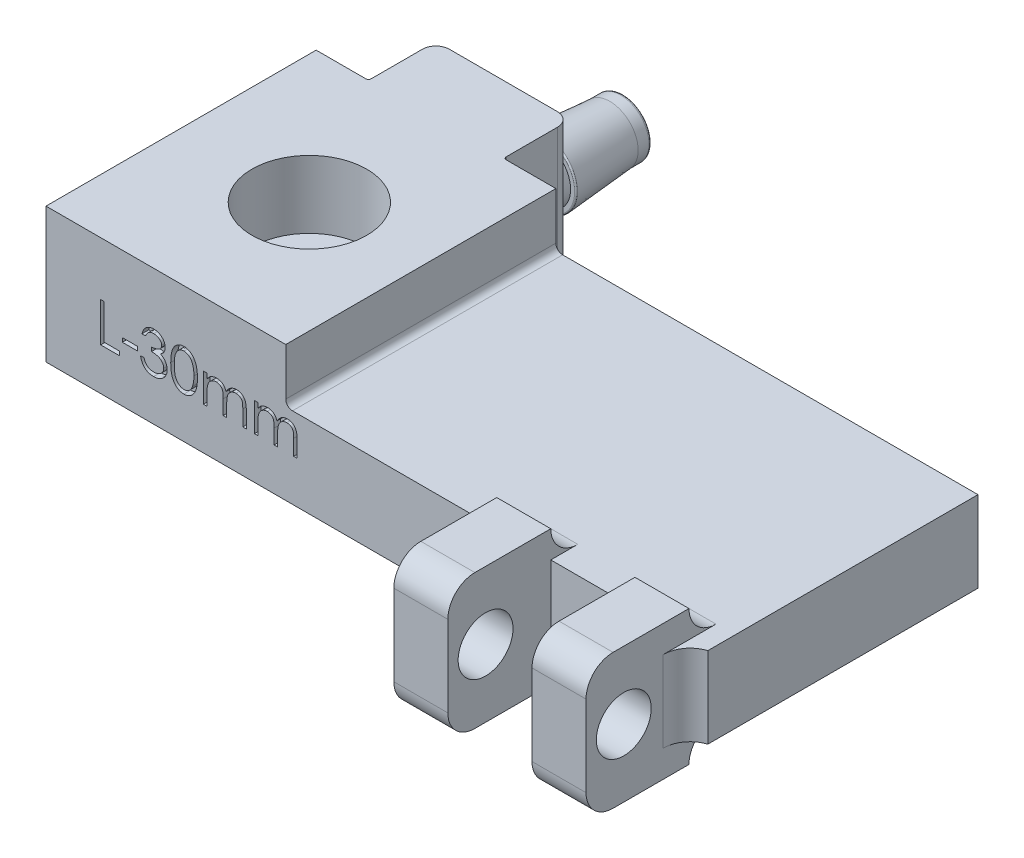
SolidWorks part; units mm, degrees
ref_plane "Front Plane" through (0, 0, 0) normal (0, 0, 1) x (1, 0, 0)
ref_plane "Top Plane" through (0, 0, 0) normal (0, 1, 0) x (1, 0, 0)
ref_plane "Right Plane" through (0, 0, 0) normal (1, 0, 0) x (0, 0, -1)
sketch "Sketch2" plane through (0, 0, 0) normal (0, 1, 0) x (1, 0, 0)
  line L1 (-14.4231, 13.5577) -> (34.5769, 13.5577)
  line L2 (-14.4231, 13.5577) -> (-14.4231, -6.4423)
  line L3 (-14.4231, -6.4423) -> (34.5769, -6.4423)
  line L4 (34.5769, 13.5577) -> (34.5769, -6.4423)
  dimension "D1" = 49
  dimension "D2" = 20
extrude "Boss-Extrude1" add sketch "Sketch2" along normal blind 10
sketch "Sketch3" plane through (0, 0, 0) normal (0, -1, 0) x (1, 0, 0)
  line L0 (34.5769, 6.4423) -> (34.5769, -13.5577) construction
  line L1 (27.5769, -5.0677) -> (-2.4231, -5.0677)
  line L2 (27.5769, -5.0677) -> (27.5769, -2.0477)
  line L3 (27.5769, -2.0477) -> (-2.4231, -2.0477)
  line L4 (-2.4231, -5.0677) -> (-2.4231, -2.0477)
  line L5 (-14.4231, -3.5577) -> (34.5769, -3.5577) construction
  line L6 (-14.4231, -13.5577) -> (-14.4231, 6.4423) construction
  dimension "D1" = 30
  dimension "D2" = 7
  dimension "D3" = 3.02
  dimension "D4" = 1.51
extrude "Cut-Extrude1" cut sketch "Sketch3" against normal blind 2
sketch "Sketch4" plane through (0, 0, 0) normal (0, -1, 0) x (1, 0, 0)
  line L0 (-2.4231, -2.0477) -> (-2.4231, -5.0677) construction
  line L1 (-2.4231, -6.5477) -> (-7.4231, -6.5477)
  line L2 (-2.4231, -6.5477) -> (-2.4231, -0.5477)
  line L3 (-2.4231, -0.5477) -> (-7.4231, -0.5477)
  line L4 (-7.4231, -6.5477) -> (-7.4231, -0.5477)
  line L6 (27.5769, -2.0477) -> (-2.4231, -2.0477) construction
  dimension "D1" = 6
  dimension "D2" = 5
  dimension "D3" = 1.5
extrude "Cut-Extrude2" cut sketch "Sketch4" against normal blind 5
sketch "Sketch5" plane through (0, 5, 0) normal (0, -1, 0) x (1, 0, 0)
  line L0 (-7.4231, -3.5477) -> (-2.4231, -3.5577) construction
  line L1 (-7.4231, -0.5477) -> (-7.4231, -6.5477) construction
  line L2 (-2.4231, -2.0477) -> (-2.4231, -5.0677) construction
  circle A0 centre (-4.9231, -3.5527) radius 4.25
  dimension "D1" = 8.5
extrude "Cut-Extrude3" cut sketch "Sketch5" against normal through all
sketch "Sketch6" plane through (0, 5, 0) normal (0, 1, 0) x (1, 0, 0)
  line L0 (-4.0731, 0.5477) -> (-2.4231, 0.5477)
  line L1 (-7.4231, 6.5477) -> (-5.7731, 6.5477)
  line L2 (-7.4231, 6.5477) -> (-7.4231, 0.5477)
  line L3 (-7.4231, 0.5477) -> (-5.7731, 0.5477)
  line L4 (-2.4231, 6.5477) -> (-2.4231, 0.5477)
  line L5 (-4.0731, 6.5477) -> (-2.4231, 6.5477)
  line L7 (-5.7731, 6.5477) -> (-5.7731, 0.5477)
  line L9 (-4.0731, 6.5477) -> (-4.0731, 0.5477)
  dimension "D1" = 1.7
extrude "Boss-Extrude2" add sketch "Sketch6" against normal blind 0.5
sketch "Sketch11" plane through (0, 0, 0) normal (0, -1, 0) x (1, 0, 0)
  circle A0 centre (28.8884, -3.5577) radius 2
  dimension "D1" = 4
extrude "Cut-Extrude4" cut sketch "Sketch11" against normal up to surface (2 mm away) up to face at (12.5769, 2, -3.5577)
sketch "Sketch12" plane through (0, 0, 0) normal (0, -1, 0) x (1, 0, 0)
  line L1 (-7.4231, -0.5477) -> (-2.4231, -0.5477)
  line L2 (-7.4231, -0.5477) -> (-7.4231, -6.5477)
  line L3 (-7.4231, -6.5477) -> (-2.4231, -6.5477)
  line L4 (-2.4231, -0.5477) -> (-2.4231, -6.5477)
extrude "Boss-Extrude4" add sketch "Sketch12" against normal blind 0.8
sketch "Sketch14" plane through (0, 0, 6.4423) normal (0, 0, 1) x (1, 0, 0)
  line L0 (-14.4231, 10) -> (34.5769, 10) construction
  line L1 (3.3269, 10) -> (34.5769, 10)
  line L2 (3.3269, 10) -> (3.3269, 6)
  line L3 (3.3269, 6) -> (34.5769, 6)
  line L4 (34.5769, 10) -> (34.5769, 6)
  line L5 (34.5769, 10) -> (34.5769, 0) construction
  line L6 (27.5769, 2) -> (-2.4231, 2) construction
  line L7 (-0.6731, 5) -> (-0.6731, 10) construction
  dimension "D1" = 4
  dimension "D2" = 4
extrude "Cut-Extrude6" cut sketch "Sketch14" against normal through all
fillet "Fillet1" radius 0.5 1 edges at (3.3269, 6, -3.5577)
sketch "Sketch13" plane through (0, 0, 6.4423) normal (0, 0, 1) x (1, 0, 0)
  line L0 (-10.748, 3.1258) -> (12.5164, 3.1258) construction
  text T0 "L-30mm" font "Century Gothic" height in points 11
extrude "Cut-Extrude5" cut sketch "Sketch13" against normal blind 0.5
sketch "Sketch17" [suppressed] plane through (0, 0, -13.5577) normal (0, 0, -1) x (-1, 0, 0)
  line L0 (-3.1673, 3.3835) -> (11.793, 3.3835) construction
  text T0 "h-2mm"
sketch "Sketch19" plane through (0, 10, 0) normal (0, 1, 0) x (1, 0, 0)
  line L0 (3.3269, 13.5577) -> (-14.4231, 13.5577) construction
  line L1 (-10.5481, 18.5477) -> (-0.5481, 18.5477)
  line L2 (-10.5481, 18.5477) -> (-10.5481, 13.5577)
  line L3 (-10.5481, 13.5577) -> (-0.5481, 13.5577)
  line L4 (-0.5481, 18.5477) -> (-0.5481, 13.5577)
  line L6 (-5.5481, -6.4423) -> (-5.5481, 18.5477) construction
  line L8 (-14.4231, -6.4423) -> (3.3269, -6.4423) construction
  dimension "D1" = 10
  dimension "D3" = 12
extrude "Boss-Extrude5" add sketch "Sketch19" against normal up to surface (10 mm away) up to face at (13.4048, 0, -3.5577)
fillet "Fillet2" radius 1 2 edges at (-10.5481, 5, -18.5477) (-0.5481, 5, -18.5477)
sketch "Sketch20" plane through (0, 0, -18.5477) normal (0, 0, -1) x (-1, 0, 0)
  line L0 (9.5481, 0) -> (1.5481, 0) construction
  circle A0 centre (4.6731, 3.5) radius 0.5
  dimension "D1" = 1
  dimension "D2" = 3.5
extrude "Cut-Extrude7" cut sketch "Sketch20" against normal up to next
sketch "Sketch21" plane through (0, 0, -18.5477) normal (0, 0, -1) x (-1, 0, 0)
  circle A0 centre (4.6731, 3.5) radius 1.4
  dimension "D1" = 2.8
extrude "Cut-Extrude8" cut sketch "Sketch21" against normal offset from surface (10 mm away) 2 up to face at (-5.1731, 3.5, -6.5477)
ref_axis "Axis1" through (-4.6731, 3.5, -8.5477) along (0, 0, -1)
ref_plane "Plane1" through (0, 3.5, 0) normal (0, -1, 0) x (-1, 0, 0)
sketch "Sketch23" plane through (0, 3.5, 0) normal (0, -1, 0) x (-1, 0, 0)
  line L0 (4.6731, 15.6131) -> (4.6731, 26.4829) construction
  line L1 (4.6731, 8.5477) -> (4.6731, 18.5477) construction
  line L2 (6.2731, 26.5477) -> (6.7731, 26.5477)
  line L3 (6.7731, 26.5477) -> (6.7731, 25.5477)
  line L4 (6.7731, 25.5477) -> (7.1731, 20.6558)
  line L5 (7.0734, 20.5477) -> (6.7731, 20.5477)
  line L6 (6.7731, 20.5477) -> (6.7731, 18.5477)
  line L7 (9.5481, 18.5477) -> (1.5481, 18.5477) construction
  line L8 (6.7731, 18.5477) -> (6.2731, 18.5477)
  line L9 (6.2731, 18.5477) -> (6.2731, 26.5477)
  arc A0 (7.0734, 20.5477) -> (7.1731, 20.6558) centre (7.0734, 20.6477) ccw
  dimension "D1" = 0.1
  dimension "D2" = 0.5
  dimension "D3" = 4.2
  dimension "D4" = 5
  dimension "D5" = 8
  dimension "D6" = 7
  dimension "D7" = 5
revolve "Revolve1" add sketch "Sketch23" angle 360 about L0
fillet "Fillet3" radius 0.2 5 edges at (-3.0731, 3.5, -26.5477) (-2.5731, 3.5, -26.5477) (-6.7731, 3.5, -18.5477)
sketch "Sketch24" plane through (0, 5, 0) normal (0, 1, 0) x (1, 0, 0)
  line L0 (-4.0731, 6.5477) -> (-4.0731, 0.5477) construction
  line L1 (-5.7731, 6.5477) -> (-4.0731, 6.5477)
  line L2 (-5.7731, 6.5477) -> (-5.7731, 5.0477)
  line L3 (-5.7731, 5.0477) -> (-4.0731, 5.0477)
  line L4 (-4.0731, 6.5477) -> (-4.0731, 5.0477)
  line L5 (-5.7731, 0.5477) -> (-5.7731, 6.5477) construction
  line L6 (-4.0731, 0.5477) -> (-5.7731, 0.5477)
  line L7 (-4.0731, 0.5477) -> (-4.0731, 2.0477)
  line L8 (-4.0731, 2.0477) -> (-5.7731, 2.0477)
  line L9 (-5.7731, 0.5477) -> (-5.7731, 2.0477)
  dimension "D1" = 1.5
  dimension "D2" = 1.5
extrude "Boss-Extrude6" add sketch "Sketch24" against normal up to vertex (0.5 mm away) up to point (-5.7731, 4.5, -0.5477)
sketch "Sketch25" plane through (0, 6, 0) normal (0, 1, 0) x (1, 0, 0)
  line L0 (29.0293, -11.4018) -> (29.0293, 13.5577) construction
  line L1 (29.0293, -14.1683) -> (29.0293, -8.6353) construction
  line L2 (3.8269, 13.5577) -> (34.5769, 13.5577) construction
  line L3 (23.0975, -11.4018) -> (23.0975, 13.5577) construction
  line L4 (23.0975, -8.6352) -> (23.0975, -14.1683) construction
  line L5 (23.0975, -6.4423) -> (29.0293, -6.4423)
  line L6 (3.8269, -6.4423) -> (34.5769, -6.4423) construction
sketch "Sketch28" plane through (0, 0, 6.4423) normal (0, 0, 1) x (1, 0, 0)
  line L1 (23.0975, 6) -> (29.0293, 6)
  line L2 (23.0975, 6) -> (23.0975, 0)
  line L3 (23.0975, 0) -> (29.0293, 0)
  line L4 (29.0293, 6) -> (29.0293, 0)
  line L5 (-14.4231, 0) -> (34.5769, 0) construction
  line L7 (18.9475, -2) -> (22.9475, -2)
  line L8 (18.9475, -2) -> (18.9475, 8)
  line L17 (18.9475, 8) -> (22.9475, 8)
  line L18 (22.9475, -2) -> (22.9475, 8)
  line L19 (18.9475, -2) -> (22.9475, 8) construction
  line L20 (18.9475, 8) -> (22.9475, -2) construction
  line L21 (33.1793, -2) -> (29.1793, -2)
  line L22 (33.1793, -2) -> (33.1793, 8)
  line L23 (33.1793, 8) -> (29.1793, 8)
  line L24 (29.1793, -2) -> (29.1793, 8)
  line L25 (33.1793, -2) -> (29.1793, 8) construction
  line L26 (33.1793, 8) -> (29.1793, -2) construction
  point P4 (20.9475, 3)
  point P15 (23.0975, 3)
  point P16 (29.0293, 3)
  point P19 (31.1793, 3)
  dimension "D1" = 10
  dimension "D2" = 4
  dimension "D3" = 0.15
  dimension "D4" = 10
  dimension "D5" = 4
  dimension "D6" = 0.15
extrude "Boss-Extrude7" add sketch "Sketch28" along normal blind 7.62 contours L2 | L4 | L7 L18 L17 L8 | L24 L21 L22 L23 region at (20.9475, 3, 6.4423) region at (31.1793, 3, 6.4423)
sketch "Sketch30" plane through (33.1793, 0, 0) normal (1, 0, 0) x (0, 0, -1)
  line L0 (-14.0623, -2) -> (-6.4423, 8) construction
  line L1 (-6.4423, 8) -> (-14.0623, 8) construction
  line L2 (-14.0623, 8) -> (-6.4423, -2) construction
  line L3 (-14.0623, -2) -> (-14.0623, 8) construction
  circle A0 centre (-11.2683, 3) radius 2.032
  point P11 (-10.2523, 3)
  dimension "D1" = 4.064
  dimension "D2" = 2.794
extrude "Cut-Extrude10" cut sketch "Sketch30" against normal up to surface (14.2318 mm away) up to face at (18.9475, 3, 8.9823)
fillet "Fillet4" radius 2 8 edges at (31.1793, -2, 14.0623) (31.1793, 8, 14.0623) (20.9475, 8, 14.0623) (20.9475, -2, 14.0623) (20.9475, 0, 6.4423) (31.1793, 0, 6.4423) (20.9475, 6, 6.4423) (31.1793, 6, 6.4423)
fillet "Fillet5" radius 2 2 edges at (18.9475, 3, 6.4423) (33.1793, 3, 6.4423)
